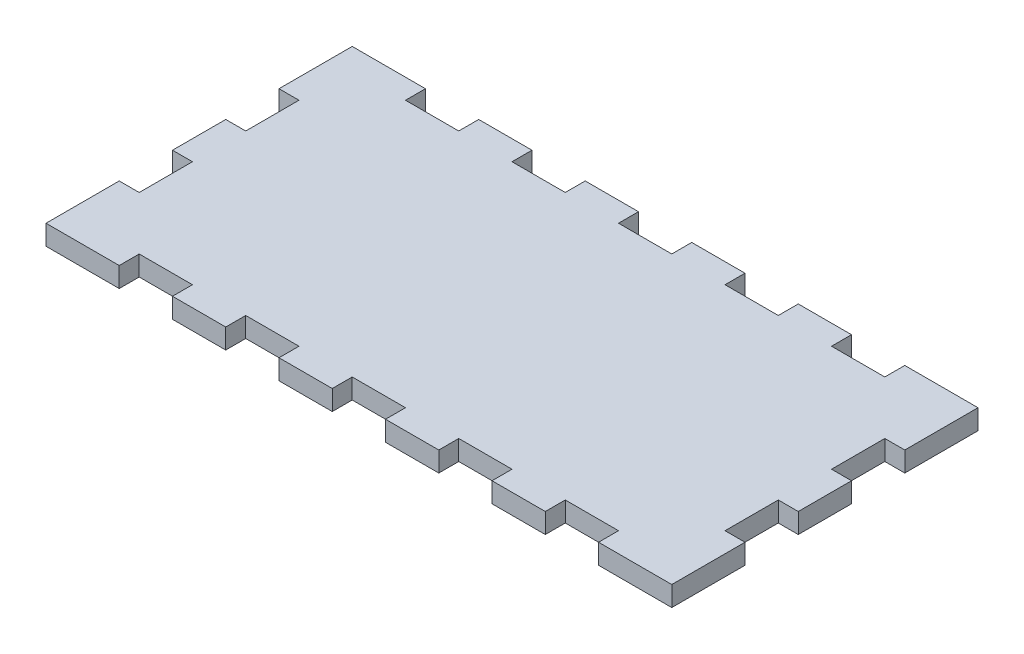
SolidWorks part; units mm, degrees
ref_plane "Front Plane" through (0, 0, 0) normal (0, 0, 1) x (1, 0, 0)
ref_plane "Top Plane" through (0, 0, 0) normal (0, 1, 0) x (1, 0, 0)
ref_plane "Right Plane" through (0, 0, 0) normal (1, 0, 0) x (0, 0, -1)
sketch "Sketch2" plane through (0, 0, 0) normal (0, 1, 0) x (1, 0, 0)
  line L1 (139.7, -63.5) -> (-139.7, -63.5)
  line L2 (139.7, -63.5) -> (139.7, 63.5)
  line L3 (139.7, 63.5) -> (-139.7, 63.5)
  line L4 (-139.7, -63.5) -> (-139.7, 63.5)
  line L5 (139.7, -63.5) -> (-139.7, 63.5) construction
  line L6 (139.7, 63.5) -> (-139.7, -63.5) construction
  point P0 (0, 0)
  dimension "D1" = 279.4
  dimension "D2" = 127
extrude "Boss-Extrude1" add sketch "Sketch2" along normal blind 9.525
sketch "Sketch3" plane through (0, 0, 63.5) normal (0, 0, 1) x (1, 0, 0)
  line L0 (-139.7, 9.525) -> (139.7, 9.525) construction
  line L1 (-139.7, 0) -> (-114.3, 0)
  line L2 (-139.7, 0) -> (-139.7, 9.525)
  line L3 (-139.7, 9.525) -> (-114.3, 9.525)
  line L4 (-114.3, 0) -> (-114.3, 9.525)
  dimension "D1" = 25.4
extrude "Boss-Extrude2" add sketch "Sketch3" along normal blind 9.525
pattern_linear "LPattern1" count 6 spacing 50.8 along (1, 0, 0) of "Boss-Extrude2"
mirror "Mirror1" about plane through (0, 0, 0) normal (0, 0, 1) of "LPattern1"
sketch "Sketch4" plane through (139.7, 0, 0) normal (1, 0, 0) x (0, 0, -1)
  line L0 (-73.025, 0) -> (73.025, 0) construction
  line L1 (-63.5, 0) -> (-38.1, 0)
  line L2 (-63.5, 0) -> (-63.5, 9.525)
  line L3 (-63.5, 9.525) -> (-38.1, 9.525)
  line L4 (-38.1, 0) -> (-38.1, 9.525)
  line L5 (-73.025, 9.525) -> (73.025, 9.525) construction
  line L6 (-73.025, 0) -> (-73.025, 9.525) construction
  dimension "D1" = 9.525
  dimension "D2" = 25.4
extrude "Boss-Extrude3" add sketch "Sketch4" along normal blind 9.525
pattern_linear "LPattern2" count 3 spacing 50.8 along (0, 0, -1) of "Boss-Extrude3"
mirror "Mirror2" about plane through (0, 0, 0) normal (1, 0, 0) of "LPattern2"
sketch "Sketch6" plane through (0, 0, 63.5) normal (0, 0, 1) x (1, 0, 0)
  line L1 (149.225, 9.525) -> (139.7, 9.525)
  line L2 (149.225, 9.525) -> (149.225, 0)
  line L3 (149.225, 0) -> (139.7, 0)
  line L4 (139.7, 9.525) -> (139.7, 0)
extrude "Boss-Extrude4" add sketch "Sketch6" along normal blind 9.525
mirror "Mirror3" about plane through (0, 0, 0) normal (1, 0, 0) of "Boss-Extrude4"
mirror "Mirror4" about plane through (0, 0, 0) normal (0, 0, 1) of "Mirror3"
